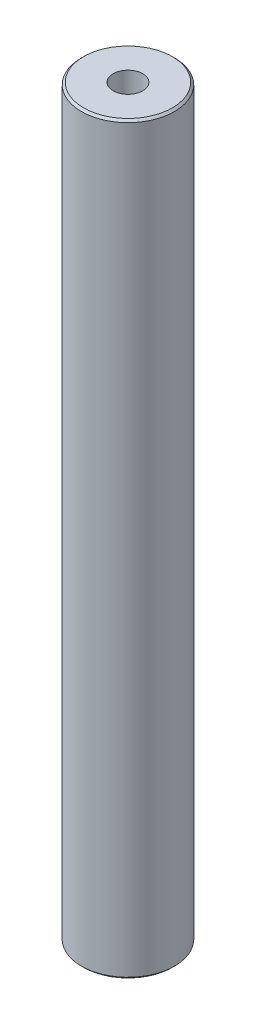
SolidWorks part; units mm, degrees
ref_plane "Front Plane" through (0, 0, 0) normal (0, 0, 1) x (1, 0, 0)
ref_plane "Top Plane" through (0, 0, 0) normal (0, 1, 0) x (1, 0, 0)
ref_plane "Right Plane" through (0, 0, 0) normal (1, 0, 0) x (0, 0, -1)
sketch "Sketch1" plane through (0, 0, 0) normal (0, 1, 0) x (1, 0, 0)
  circle A0 centre (0, 0) radius 37.5
  dimension "SHAFT_OD" = 75
extrude "Boss-Extrude1" add sketch "Sketch1" along normal blind 600
sketch "Sketch2" plane through (0, 0, 0) normal (0, 1, 0) x (1, 0, 0)
  circle A0 centre (0, 0) radius 11.9451
  dimension "BORE_D" = 23.8902
extrude "Cut-Extrude1" cut sketch "Sketch2" along normal through all
chamfer "Chamfer1" distance 1.7173 angle 45 2 edges at (0, 600, 37.5) (0, 0, 37.5)
